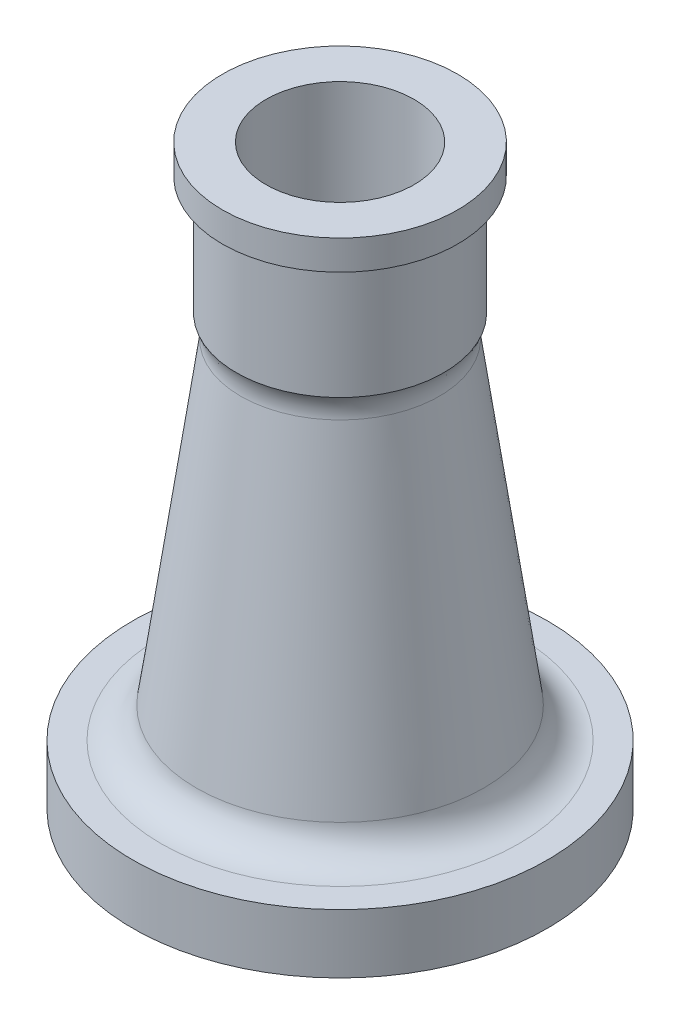
SolidWorks part; units mm, degrees
ref_plane "Front Plane" through (0, 0, 0) normal (0, 0, 1) x (1, 0, 0)
ref_plane "Top Plane" through (0, 0, 0) normal (0, 1, 0) x (1, 0, 0)
ref_plane "Right Plane" through (0, 0, 0) normal (1, 0, 0) x (0, 0, -1)
sketch "Sketch2" plane through (0, 0, 0) normal (0, 0, 1) x (1, 0, 0)
  line L0 (39.7259, 131.0264) -> (35, 131.0264)
  line L1 (35, 131.0264) -> (35, 91.0264)
  line L2 (35, 91.0264) -> (32.5, 91.0264)
  line L3 (32.5, 91.0264) -> (50, -33.9736)
  line L4 (0, -92.5) -> (0, 131.0264) construction
  line L5 (50, -33.9736) -> (70, -33.9736)
  line L6 (70, -33.9736) -> (70, -53.9736)
  point P2 (0, 0)
  dimension "D1" = 35
  dimension "D2" = 32.5
  dimension "D3" = 50
  dimension "D4" = 125
  dimension "D5" = 40
  dimension "D6" = 20
  dimension "D7" = 70
revolve "Revolve-Thin2" add sketch "Sketch2" angle 360 about L4
fillet "Fillet1" radius 12 1 edges at (0, 91.0264, -32.5)
fillet "Fillet2" radius 12 1 edges at (0, -33.9736, -50)
